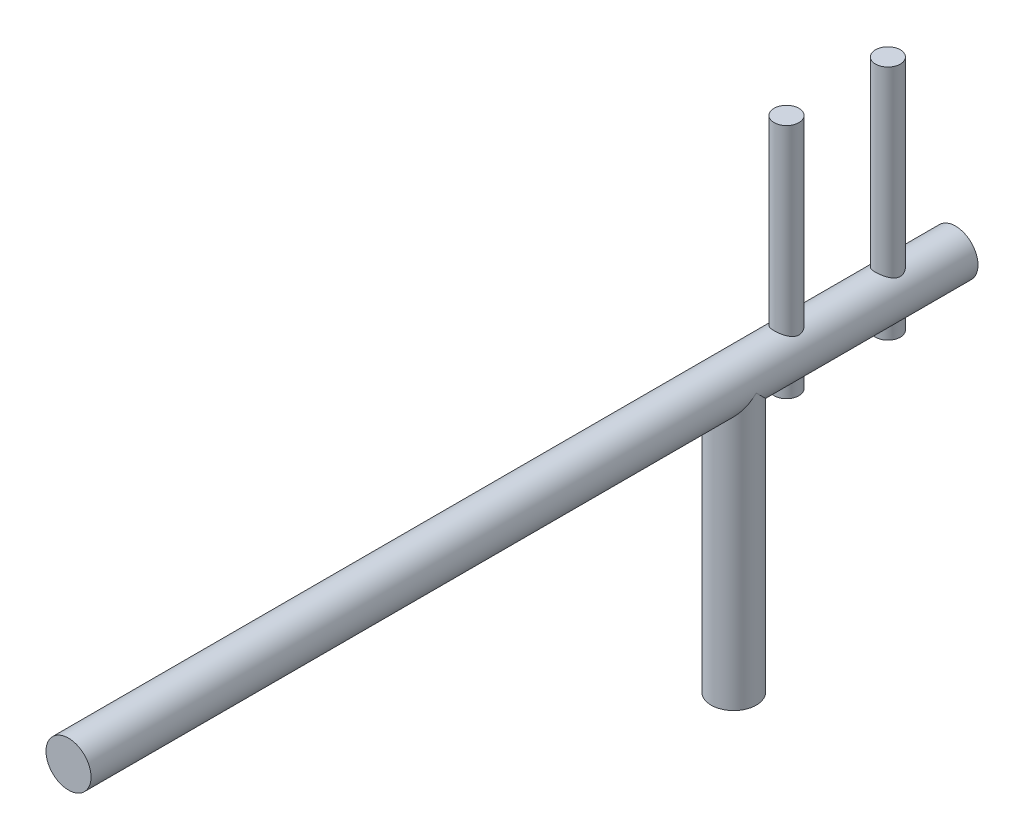
SolidWorks part; units mm, degrees
material "Maple"
ref_plane "Front Plane" through (0, 0, 0) normal (0, 0, 1) x (1, 0, 0)
ref_plane "Top Plane" through (0, 0, 0) normal (0, 1, 0) x (1, 0, 0)
ref_plane "Right Plane" through (0, 0, 0) normal (1, 0, 0) x (0, 0, -1)
sketch "Sketch1" plane through (0, 0, 0) normal (0, 1, 0) x (1, 0, 0)
  circle A0 centre (0, 0) radius 6.35
  dimension "D1" = 12.7
extrude "Boss-Extrude1" add sketch "Sketch1" along normal blind 76.2
sketch "Sketch2" plane through (0, 0, 0) normal (0, 0, 1) x (1, 0, 0)
  line L0 (6.35, 76.2) -> (-6.35, 76.2) construction
  circle A0 centre (0, 76.2) radius 6.35
extrude "Boss-Extrude2" add sketch "Sketch2" along normal blind 187.5 and the other way blind 62.5
sketch "Sketch3" plane through (0, 0, 0) normal (0, 1, 0) x (1, 0, 0)
  line L0 (0, 0) -> (0, 111.0056) construction
  line L1 (6.35, 62.5) -> (-6.35, 62.5) construction
  circle A0 centre (0, 14.875) radius 3.5
  circle A1 centre (0, 43.45) radius 3.5
  dimension "D2" = 7
  dimension "D3" = 28.575
  dimension "D4" = 7
  dimension "D1" = 19.05
extrude "Boss-Extrude3" add sketch "Sketch3" along normal blind 66.675 from offset 66.675
